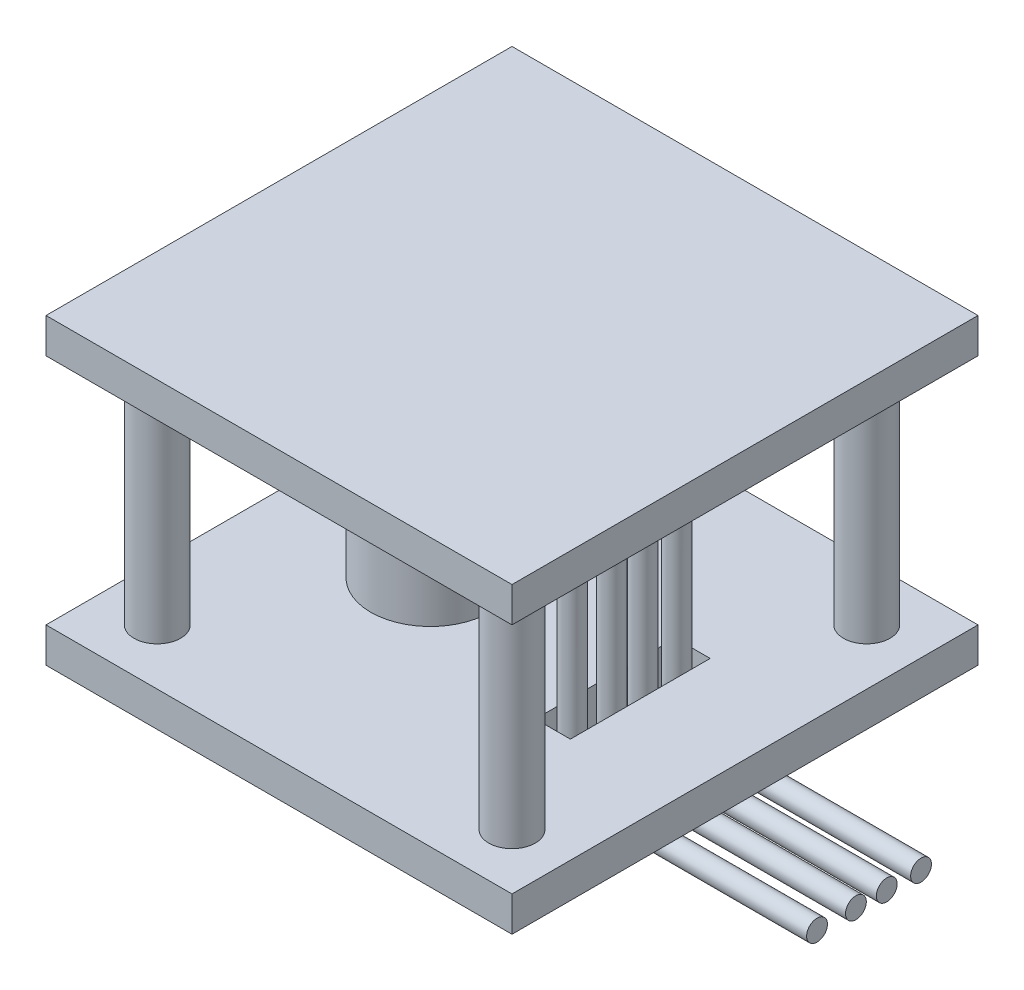
SolidWorks part; units mm, degrees
ref_plane "前视基准面" through (0, 0, 0) normal (0, 0, 1) x (1, 0, 0)
ref_plane "上视基准面" through (0, 0, 0) normal (0, 1, 0) x (1, 0, 0)
ref_plane "右视基准面" through (0, 0, 0) normal (1, 0, 0) x (0, 0, -1)
sketch "草图2" plane through (0, 0, 0) normal (0, 1, 0) x (1, 0, 0)
  line L0 (0, 0) -> (31.047, 0) construction
  line L1 (-9.75, -9.75) -> (9.75, -9.75)
  line L2 (-9.75, -9.75) -> (-9.75, 9.75)
  line L3 (-9.75, 9.75) -> (9.75, 9.75)
  line L4 (9.75, -9.75) -> (9.75, 9.75)
  line L5 (-9.75, -9.75) -> (9.75, 9.75) construction
  line L6 (-9.75, 9.75) -> (9.75, -9.75) construction
  line L7 (-20, -20) -> (20, -20)
  line L8 (-20, -20) -> (-20, 20)
  line L9 (-20, 20) -> (20, 20)
  line L10 (20, -20) -> (20, 20)
  line L11 (-20, -20) -> (20, 20) construction
  line L12 (-20, 20) -> (20, -20) construction
  line L13 (0, 0) -> (0, 17.7315) construction
  circle A0 centre (15.2248, 15.2248) radius 2
  circle A1 centre (-15.2248, -15.2248) radius 2
  circle A2 centre (15.2248, -15.2248) radius 2
  circle A3 centre (-15.2248, 15.2248) radius 2
  point P0 (0, 0)
  point P6 (0, 0)
  point P22 (20, -20)
  dimension "D5" = 4
  dimension "D1" = 19.5
  dimension "D2" = 19.5
  dimension "D3" = 40
  dimension "D4" = 40
  dimension "D6" = 21.5311
extrude "凸台-拉伸2" add sketch "草图2" along normal blind 3 contours L8 L9 L10 L7
sketch "草图3" plane through (0, 0, 0) normal (0, 1, 0) x (1, 0, 0)
  line L7 (8, 6.0116) -> (11, 6.0116)
  line L8 (8, 6.0116) -> (8, -5.9884)
  line L9 (8, -5.9884) -> (11, -5.9884)
  line L10 (11, 6.0116) -> (11, -5.9884)
  circle A0 centre (-15.2248, -15.2248) radius 2 construction
  circle A1 centre (15.2248, -15.2248) radius 2 construction
  circle A2 centre (15.2248, 15.2248) radius 2 construction
  circle A3 centre (-15.2248, 15.2248) radius 2 construction
  circle A4 centre (-15.2248, -15.2248) radius 2
  circle A5 centre (15.2248, -15.2248) radius 2
  circle A6 centre (15.2248, 15.2248) radius 2
  circle A7 centre (-15.2248, 15.2248) radius 2
  circle A8 centre (-7, 0) radius 5.125
  point P27 (8, 0.0116)
  dimension "D1" = 10.25
  dimension "D2" = 8
  dimension "D5" = 12
  dimension "D6" = 3
extrude "切除-拉伸1" cut sketch "草图3" along normal blind 3
sketch "草图4" plane through (0, 0, 0) normal (0, 1, 0) x (1, 0, 0)
  line L0 (0, 0) -> (31.047, 0) construction
  circle A0 centre (3, 0) radius 2
  dimension "D1" = 4
  dimension "D2" = 3
extrude "凸台-拉伸3" add sketch "草图4" against normal blind 2
sketch "草图9" plane through (0, 3, 0) normal (0, 1, 0) x (1, 0, 0)
  line L1 (20, -20) -> (-20, -20)
  line L2 (20, -20) -> (20, 20)
  line L3 (20, 20) -> (-20, 20)
  line L4 (-20, -20) -> (-20, 20)
extrude "凸台-拉伸4" add sketch "草图9" along normal blind 3 from offset 20 separate body
extrude "凸台-拉伸5" add sketch "草图3<3>" along normal blind 24 contours A4 | A7 | A6 | A5
sketch "草图3<3>" plane through (0, 0, 0) normal (0, 1, 0) x (1, 0, 0) same geometry as "草图3"
extrude "凸台-拉伸6" add sketch "草图2<8>" against normal blind 2 contours A0 | A3 | A1 | A2
sketch "草图2<8>" plane through (0, 0, 0) normal (0, 1, 0) x (1, 0, 0) same geometry as "草图2"
sketch "草图11" plane through (0, 23, 0) normal (0, -1, 0) x (1, 0, 0)
  line L1 (-14.325, -7.9352) -> (14.325, -7.9352)
  line L2 (-14.325, -7.9352) -> (-14.325, 7.9352)
  line L3 (-14.325, 7.9352) -> (14.325, 7.9352)
  line L4 (14.325, -7.9352) -> (14.325, 7.9352)
  line L5 (-14.325, -7.9352) -> (14.325, 7.9352) construction
  line L6 (-14.325, 7.9352) -> (14.325, -7.9352) construction
  point P0 (0, 0)
  point P6 (-14.325, -7.9352)
extrude "凸台-拉伸7" add sketch "草图11" along normal blind 2
sketch "草图12" plane through (0, 3, 0) normal (0, 1, 0) x (1, 0, 0)
  circle A0 centre (-7, 0) radius 5.125 construction
  circle A1 centre (-7, 0) radius 5.125
extrude "凸台-拉伸8" add sketch "草图12" along normal blind 18 and the other way blind 5
sketch "草图13" plane through (0, 21, 0) normal (0, -1, 0) x (1, 0, 0)
  line L0 (11, 5.9884) -> (11, -6.0116) construction
  line L1 (11, 5.9884) -> (11, -6.0116)
  line L2 (11, -6.0116) -> (8, -6.0116) construction
  line L3 (8, 5.9884) -> (11, 5.9884) construction
  line L4 (14.325, -7.9352) -> (14.325, 7.9352)
  line L5 (14.325, 7.9352) -> (-14.325, 7.9352)
  line L6 (-14.325, 7.9352) -> (-14.325, -7.9352)
  line L7 (-14.325, -7.9352) -> (14.325, -7.9352)
  line L8 (14.325, -7.9352) -> (14.325, 7.9352)
  line L9 (14.325, 7.9352) -> (-14.325, 7.9352)
  line L10 (-14.325, 7.9352) -> (-14.325, -7.9352)
  line L11 (-14.325, -7.9352) -> (14.325, -7.9352)
  line L12 (8, -6.0116) -> (8, 5.9884) construction
  line L13 (11, -6.0116) -> (8, -6.0116)
  line L14 (11, 5.9884) -> (11, -6.0116)
  line L15 (8, 5.9884) -> (11, 5.9884)
  line L16 (8, -6.0116) -> (8, 5.9884)
  dimension "D1" = 0
extrude "凸台-拉伸9" add sketch "草图13" along normal blind 3 contours L16 L13 L1 L15 | L14 L1 region at (9.5, 21, -0.0116)
sketch "草图14" plane through (0, 18, 0) normal (0, -1, 0) x (1, 0, 0)
  line L1 (11, -6.0116) -> (8, -6.0116) construction
  circle A2 centre (9.6122, 1.0342) radius 0.9263
  circle A4 centre (9.5395, -4.5935) radius 0.9263
  circle A5 centre (9.6122, -1.6304) radius 0.9263
  circle A6 centre (9.5395, 4.3493) radius 0.9263
  point P2 (9.5395, -4.5935)
  point P8 (9.5395, -1.9616)
  point P9 (9.5395, 0.6486)
  point P10 (9.5395, -2.6735)
  point P12 (9.5395, 4.3493)
  point P13 (9.6122, -1.6304)
  point P14 (0, 0)
  dimension "D1" = 1.4181
extrude "凸台-拉伸10" add sketch "草图14" along normal blind 21
sketch "草图16" plane through (0, 0, 0) normal (1, 0, 0) x (0, 0, -1)
  circle A0 centre (-4.3167, -2.2841) radius 0.8937
  circle A1 centre (-0.9811, -2.2841) radius 0.8937
  circle A2 centre (1.6678, -2.2841) radius 0.8937
  circle A3 centre (4.611, -2.2841) radius 0.8937
  point P4 (-0.9811, -2.2841)
  point P7 (1.6678, -2.2841)
  point P10 (4.611, -2.2841)
extrude "凸台-拉伸11" add sketch "草图16" along normal blind 21 from offset 9.5
